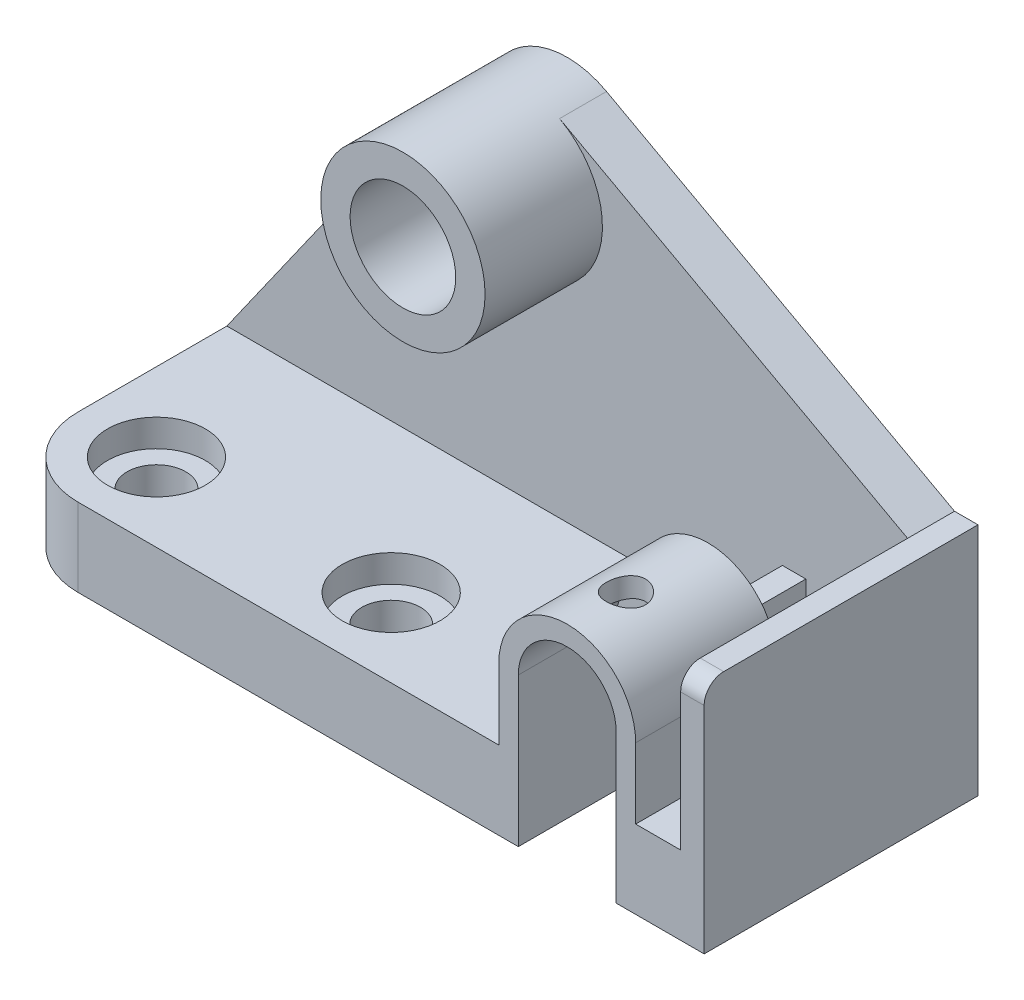
SolidWorks part; units mm, degrees
ref_plane "Front Plane" through (0, 0, 0) normal (0, 0, 1) x (1, 0, 0)
ref_plane "Top Plane" through (0, 0, 0) normal (0, 1, 0) x (1, 0, 0)
ref_plane "Right Plane" through (0, 0, 0) normal (1, 0, 0) x (0, 0, -1)
sketch "Sketch1" plane through (0, 0, 0) normal (0, 0, 1) x (1, 0, 0)
  line L0 (-17.1678, 12.0941) -> (-75, -70)
  line L1 (-75, -70) -> (-75, -90)
  line L2 (-75, -90) -> (57.5, -90)
  line L3 (-75, -70) -> (52.5, -70)
  line L4 (99, -70) -> (99, -30)
  line L5 (105, -33.2674) -> (105, -30)
  line L6 (99, -30) -> (105, -30)
  line L7 (105, -90) -> (105, -33.2674)
  line L8 (99, -30) -> (10.0432, 18.4427)
  line L9 (57.5, -52) -> (57.5, -90)
  line L10 (82.5, -52) -> (82.5, -90)
  line L11 (87.5, -52) -> (87.5, -70)
  line L12 (52.5, -52) -> (52.5, -70)
  line L13 (52.5, -52) -> (52.5, -90) construction
  line L14 (87.5, -52) -> (87.5, -90) construction
  line L15 (87.5, -70) -> (99, -70)
  line L16 (82.5, -90) -> (105, -90)
  line L17 (57.5, -90) -> (82.5, -90)
  circle A2 centre (0, 0) radius 21
  arc A4 (82.5, -52) -> (57.5, -52) centre (70, -52) ccw
  arc A5 (87.5, -52) -> (52.5, -52) centre (70, -52) ccw
  dimension "D3" = 42
  dimension "D6" = 20
  dimension "D9" = 25
  dimension "D4" = 90
  dimension "D5" = 105
  dimension "D7" = 180
  dimension "D8" = 60
  dimension "D10" = 35
  dimension "D12" = 5
  dimension "D11" = 38
extrude "Boss-Extrude1" add sketch "Sketch1" along normal blind 42 contours A2 region at (0, 0, 0)
extrude "Boss-Extrude2" add sketch "Sketch1<3>" along normal blind 12 contours L2 L7 L8 A2 L0 L3 region at (13.3488, -38.7868, 0)
sketch "Sketch1<3>" plane through (0, 0, 0) normal (0, 0, 1) x (1, 0, 0) same geometry as "Sketch1"
extrude "Boss-Extrude5" add sketch "Sketch1<7>" along normal blind 70 contours L2 L7 L5 L6 L4 L3 L1 | L10 A4 L9 L17 region at (19.3239, -74.8109, 0) region at (70, -66.0099, 0)
sketch "Sketch1<7>" plane through (0, 0, 0) normal (0, 0, 1) x (1, 0, 0) same geometry as "Sketch1"
sketch "Sketch2" plane through (0, 0, 0) normal (0, 1, 0) x (1, 0, 0)
  line L0 (52.5, -12) -> (52.5, -34)
  line L1 (52.5, -70) -> (52.5, -12) construction
  line L2 (52.5, -34) -> (87.5, -34)
  line L3 (87.5, -70) -> (87.5, -12) construction
  line L4 (87.5, -34) -> (87.5, -12)
  line L5 (87.5, -12) -> (52.5, -12)
  dimension "D1" = 22
extrude "Cut-Extrude2" cut sketch "Sketch2" against normal blind 70 contours L5 L0 L2 L4
sketch "Sketch3" plane through (0, 0, 70) normal (0, 0, 1) x (1, 0, 0)
  line L0 (57.5, -52) -> (57.5, -90)
  line L1 (-75, -90) -> (105, -90) construction
  line L2 (82.5, -52) -> (82.5, -90)
  line L3 (82.5, -90) -> (57.5, -90)
  line L5 (67, -52) -> (73, -52)
  line L6 (67, -52) -> (67, -70)
  line L7 (67, -70) -> (73, -70)
  line L8 (73, -52) -> (73, -70)
  arc A0 (82.5, -52) -> (57.5, -52) centre (70, -52) ccw
  point P12 (70, -52)
  point P13 (0, 0)
  dimension "D1" = 25
  dimension "D2" = 6
extrude "Cut-Extrude4" cut sketch "Sketch3" against normal blind 25 and the other way through all contours A0 L0 L3 L2
sketch "Sketch5" plane through (0, 0, 45) normal (0, 0, 1) x (1, 0, 0)
  line L1 (67, -52) -> (73, -52)
  line L2 (67, -52) -> (67, -70)
  line L3 (67, -70) -> (73, -70)
  line L4 (73, -52) -> (73, -70)
  point P4 (70, -52)
  dimension "D1" = 6
extrude "Boss-Extrude6" add sketch "Sketch5" against normal up to surface (33 mm away) up to face at (24.8418, -35.0365, 12)
fillet "Fillet1" radius 5 1 edges at (102, -30, 70)
sketch "Sketch7" plane through (0, -70, 0) normal (0, 1, 0) x (1, 0, 0)
  line L0 (-75, -70) -> (52.5, -70) construction
  line L1 (-75, -70) -> (-75, -12) construction
  circle A0 centre (-55, -50) radius 20
  circle A1 centre (-55, -50) radius 12.5
  circle A2 centre (-55, -50) radius 7.5
  circle A3 centre (5, -50) radius 7.5
  circle A4 centre (5, -50) radius 12.5
  dimension "D1" = 40
  dimension "D2" = 25
  dimension "D3" = 15
  dimension "D4" = 25
  dimension "D5" = 15
  dimension "D6" = 60
sketch "Sketch8" plane through (0, 0, 45) normal (0, 0, 1) x (1, 0, 0)
  line L0 (82.5, -52) -> (82.5, -90) construction
  line L1 (57.5, -90) -> (82.5, -90)
  line L2 (57.5, -90) -> (57.5, -84)
  line L3 (57.5, -84) -> (82.5, -84)
  line L4 (82.5, -90) -> (82.5, -84)
  dimension "D1" = 6
extrude "Cut-Extrude6" cut sketch "Sketch8" against normal blind 167
extrude "Cut-Extrude7" cut sketch "Sketch7" against normal blind 167 contours A2
extrude "Cut-Extrude8" cut sketch "Sketch7<3>" against normal blind 7 contours A1
sketch "Sketch7<3>" plane through (0, -70, 0) normal (0, 1, 0) x (1, 0, 0) same geometry as "Sketch7"
fillet "Fillet2" radius 20 1 edges at (-75, -80, 70)
extrude "Cut-Extrude9" cut sketch "Sketch7<4>" against normal blind 7 contours A4 A3 region at (-7.1464, -70, 50)
sketch "Sketch7<4>" plane through (0, -70, 0) normal (0, 1, 0) x (1, 0, 0) same geometry as "Sketch7"
extrude "Cut-Extrude10" cut sketch "Sketch7<5>" against normal through all contours A3 region at (5, -70, 50)
sketch "Sketch7<5>" plane through (0, -70, 0) normal (0, 1, 0) x (1, 0, 0) same geometry as "Sketch7"
sketch "Sketch10" plane through (0, 0, 0) normal (0, 1, 0) x (1, 0, 0)
  line L0 (0, 0) -> (0, -42.2253)
  line L1 (0, -42.2253) -> (13.5, -42.2253)
  line L2 (13.5, -42.2253) -> (13.5, -20.8305)
  line L3 (13.5, -20.8305) -> (7.5, -17.2253)
  line L4 (7.5, -17.2253) -> (7.5, 0)
  line L5 (-75, 0) -> (57.5, 0) construction
  line L6 (0, 0) -> (7.5, 0)
  point P3 (0, 0)
  point P10 (0, 0)
  dimension "D1" = 7.5
  dimension "D2" = 13.5
  dimension "D3" = 59
  dimension "D4" = 25
revolve "Cut-Revolve1" cut sketch "Sketch10" angle 360 about L0
sketch "Sketch11" plane through (0, 0, 0) normal (0, 1, 0) x (1, 0, 0)
  circle A0 centre (70, -55) radius 5
  point P2 (0, 0)
  dimension "D1" = 10
  dimension "D2" = 15
extrude "Cut-Extrude11" cut sketch "Sketch11" against normal blind 80
